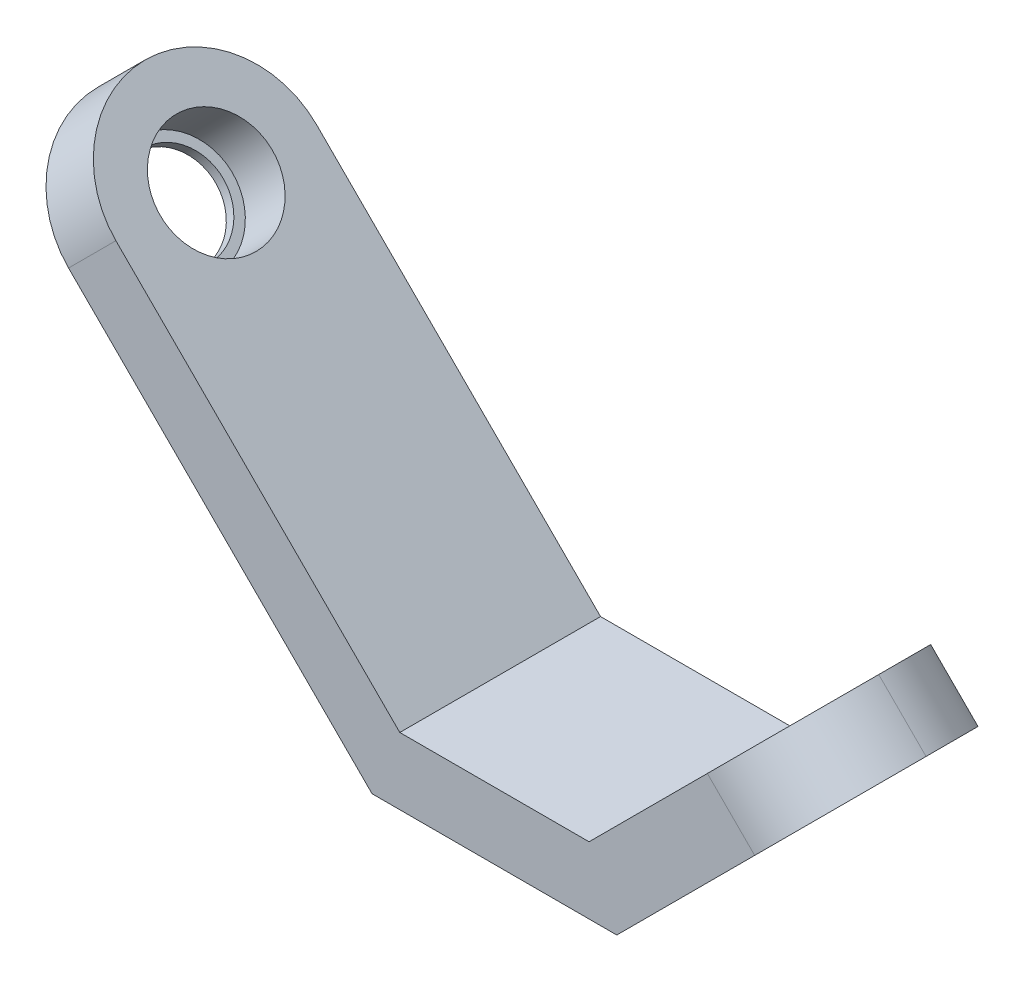
SolidWorks part; units mm, degrees
ref_plane "正面" through (0, 0, 0) normal (0, 0, 1) x (1, 0, 0)
ref_plane "平面" through (0, 0, 0) normal (0, 1, 0) x (1, 0, 0)
ref_plane "右側面" through (0, 0, 0) normal (1, 0, 0) x (0, 0, -1)
sketch "ｽｹｯﾁ1" plane through (0, 0, 0) normal (0, 0, 1) x (1, 0, 0)
  line L0 (0, 0) -> (-27.981, 27.981)
  line L1 (-27.981, 27.981) -> (-24.4454, 31.5165)
  line L2 (-24.4454, 31.5165) -> (2.0711, 5)
  line L3 (2.0711, 5) -> (16.2132, 5)
  line L4 (16.2132, 5) -> (30.3553, 19.1421)
  line L5 (30.3553, 19.1421) -> (33.8909, 15.6066)
  line L6 (33.8909, 15.6066) -> (18.2843, 0)
  line L7 (18.2843, 0) -> (0, 0)
  point P6 (23.2843, 12.0711)
  point P10 (-19.1421, 26.2132)
  dimension "D1" = 135
  dimension "D2" = 135
  dimension "D3" = 5
  dimension "D4" = 5
  dimension "D5" = 5
  dimension "D8" = 25
  dimension "D6" = 7.5
  dimension "D7" = 45
  dimension "D9" = 20
extrude "ﾎﾞｽ - 押し出し1" add sketch "ｽｹｯﾁ1" along normal mid plane 15
sketch "ｽｹｯﾁ2" plane through (0, 0, 0) normal (-0.7071, -0.7071, 0) x (0, 0, 1)
  line L1 (7.5, 39.5711) -> (-7.5, 39.5711) construction
  circle A0 centre (0, 32.0711) radius 4.2
  dimension "D1" = 8.4
  dimension "D2" = 7.5
extrude "ｶｯﾄ - 押し出し1" cut sketch "ｽｹｯﾁ2" against normal through all both and the other way through all
sketch "ｽｹｯﾁ3" plane through (9.1421, -9.1421, 0) normal (0.7071, -0.7071, 0) x (0, 0, -1)
  line L1 (-7.5, 35) -> (7.5, 35) construction
  circle A0 centre (0, 27.5) radius 4.2
  point P7 (0, 35)
  dimension "D1" = 8.4
  dimension "D2" = 7.5
extrude "ｶｯﾄ - 押し出し2" cut sketch "ｽｹｯﾁ3" against normal through all both and the other way through all
fillet "ﾌｨﾚｯﾄ1" radius 7.5 4 edges at (32.1231, 17.3744, -7.5) (32.1231, 17.3744, 7.5) (-26.2132, 29.7487, -7.5) (-26.2132, 29.7487, 7.5)
sketch "ｽｹｯﾁ4" plane through (0, 0, 0) normal (0.7071, 0.7071, 0) x (0, 0, -1)
  circle A0 centre (0, 32.0711) radius 4.2 construction
  circle A1 centre (0, 32.0711) radius 4.2
  circle A2 centre (0, 32.0711) radius 3.5
  dimension "D1" = 7
extrude "ﾎﾞｽ - 押し出し2" add sketch "ｽｹｯﾁ4" along normal blind 0.8
sketch "ｽｹｯﾁ5" plane through (9.1421, -9.1421, 0) normal (-0.7071, 0.7071, 0) x (0, 0, 1)
  circle A0 centre (0, 27.5) radius 4.2 construction
  circle A1 centre (0, 27.5) radius 4.2
  circle A2 centre (0, 27.5) radius 3.5
  dimension "D1" = 7
extrude "ﾎﾞｽ - 押し出し3" add sketch "ｽｹｯﾁ5" along normal blind 0.8
equation "\"D4@ｽｹｯﾁ1\"=\"D3@ｽｹｯﾁ1\""
equation "\"D5@ｽｹｯﾁ1\"=\"D3@ｽｹｯﾁ1\""
